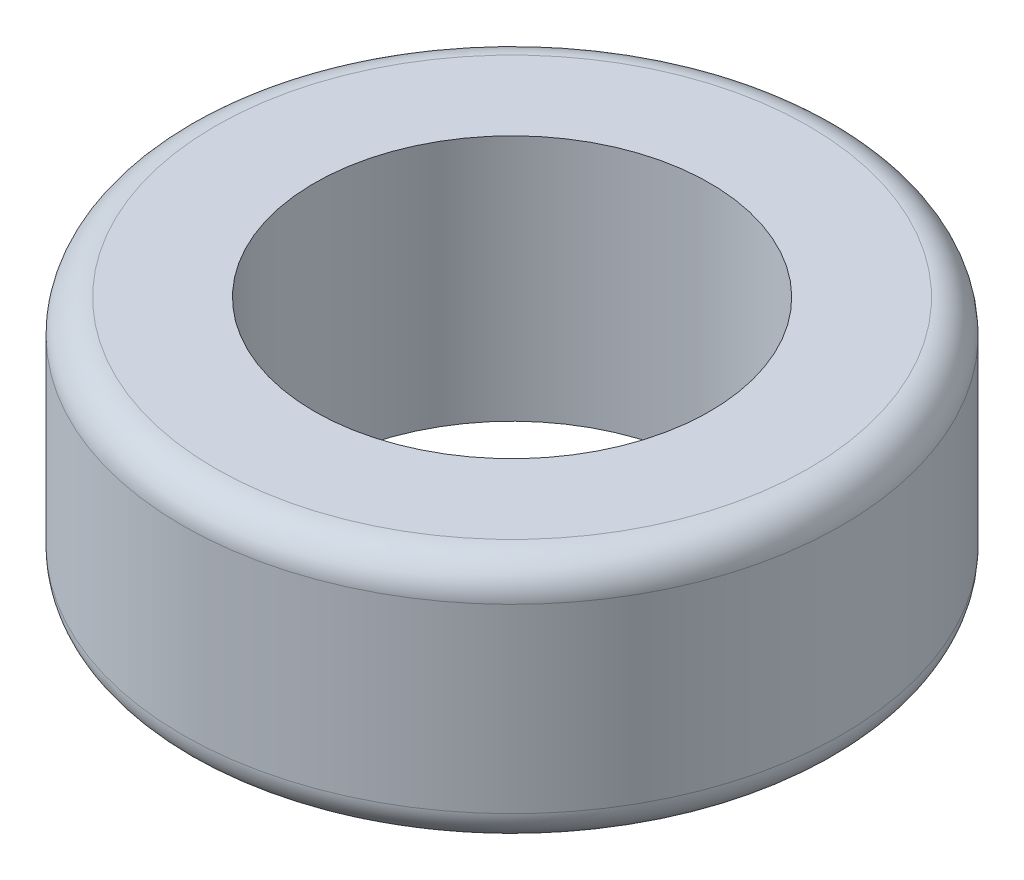
SolidWorks part; units mm, degrees
ref_plane "Front Plane" through (0, 0, 0) normal (0, 0, 1) x (1, 0, 0)
ref_plane "Top Plane" through (0, 0, 0) normal (0, 1, 0) x (1, 0, 0)
ref_plane "Right Plane" through (0, 0, 0) normal (1, 0, 0) x (0, 0, -1)
ref_axis "X-Axis" through (88.99, 0, 0) along (-1, 0, 0)
ref_axis "Y-Axis" through (0, 0, -88.99) along (0, 0, 1)
ref_axis "Z-Axis" through (0, -55, 0) along (0, 1, 0)
sketch "Sketch1" plane through (0, 0, 0) normal (0, 1, 0) x (1, 0, 0)
  circle A0 centre (0, 0) radius 6
  circle A1 centre (0, 0) radius 10
  dimension "D1" = 12
  dimension "D2" = 4
extrude "Boss-Extrude1" add sketch "Sketch1" along normal blind 7.5
fillet "Fillet1" radius 1 2 edges at (0, 0, 10) (0, 7.5, 10)
